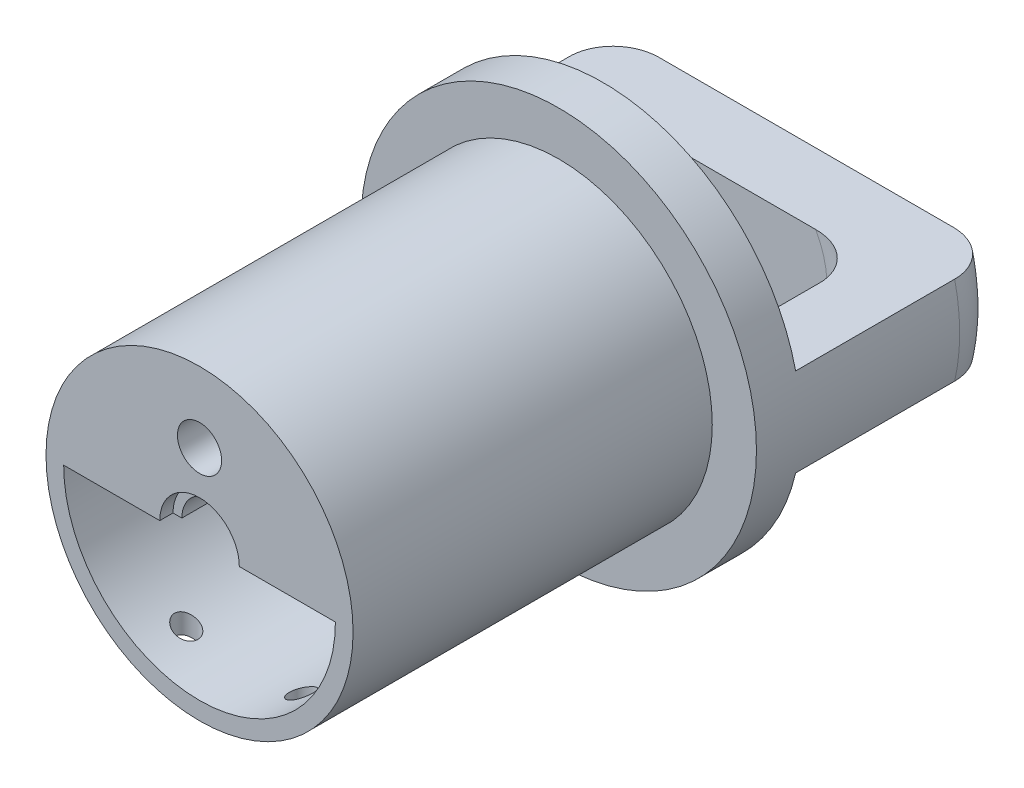
SolidWorks part; units mm, degrees
ref_plane "Plan de face" through (0, 0, 0) normal (0, 0, 1) x (1, 0, 0)
ref_plane "Plan de dessus" through (0, 0, 0) normal (0, 1, 0) x (1, 0, 0)
ref_plane "Plan de droite" through (0, 0, 0) normal (1, 0, 0) x (0, 0, -1)
sketch "Esquisse1" plane through (0, 0, 0) normal (0, 0, 1) x (1, 0, 0)
  circle A0 centre (0, 0) radius 34.75
  circle A1 centre (0, 0) radius 30.75
  dimension "D1" = 69.5
  dimension "D2" = 4
extrude "Boss.-Extru.1" add sketch "Esquisse1" along normal blind 91.3
sketch "Esquisse2" plane through (0, 0, 0) normal (0, 0, 1) x (1, 0, 0)
  circle A0 centre (0, 0) radius 34.75
  circle A2 centre (0, 0) radius 44.75
  circle A4 centre (0, 0) radius 34.75 construction
  dimension "D1" = 10
extrude "Boss.-Extru.2" add sketch "Esquisse2" along normal blind 10
sketch "Esquisse3" plane through (0, 0, 91.3) normal (0, 0, 1) x (1, 0, 0)
  circle A0 centre (0, 0) radius 45
extrude "Boss.-Extru.3" add sketch "Esquisse3" against normal blind 20
sketch "Esquisse4" plane through (0, 0, 0) normal (0, 1, 0) x (1, 0, 0)
  line L0 (0, -96.3) -> (0, -71.3) construction
  line L1 (-11.15, -96.3) -> (11.15, -96.3) construction
  line L2 (30.75, -71.3) -> (-30.75, -71.3) construction
  line L3 (0, -78.6) -> (-9, -78.6) construction
  line L5 (8, -78.6) -> (-8, -78.6) construction
  line L6 (-9, -78.6) -> (-9, -82.3)
  line L7 (-9, -82.3) -> (-7, -82.3)
  line L8 (-7, -82.3) -> (-7, -88.3)
  line L9 (-7, -88.3) -> (-9, -88.3)
  line L10 (-9, -88.3) -> (-9, -91.3)
  line L11 (-9, -91.3) -> (-7.25, -91.3)
  line L12 (-7.25, -91.3) -> (-7.25, -92.8)
  line L13 (-7.25, -92.8) -> (-9, -92.8)
  line L14 (-9, -92.8) -> (-9, -93.8)
  line L15 (-9, -93.8) -> (-7.25, -93.8)
  line L16 (-7.25, -93.8) -> (-7.25, -95.3)
  line L17 (-7.25, -95.3) -> (-12.15, -95.3)
  line L18 (-12.15, -95.3) -> (-12.15, -96.3)
  line L19 (-12.15, -96.3) -> (0, -96.3)
  line L20 (0, -96.3) -> (0, -71.3)
  line L21 (0, -71.3) -> (-10, -71.3)
  line L22 (-10, -71.3) -> (-9, -78.6)
  dimension "D1" = 10
  dimension "D2" = 9
  dimension "D3" = 7
  dimension "D4" = 9
  dimension "D5" = 7.25
  dimension "D6" = 9
  dimension "D7" = 7.25
  dimension "D8" = 12.15
  dimension "D9" = 3.7
  dimension "D10" = 6
  dimension "D11" = 1.5
  dimension "D12" = 1
  dimension "D13" = 3
  dimension "D14" = 1
revolve "Enlèvement de matière-Révolution1" cut sketch "Esquisse4" angle 360 about L20
sketch "Esquisse5" plane through (0, 0, 71.3) normal (0, 0, -1) x (-1, 0, 0)
  line L0 (-30.75, 0) -> (30.75, 0)
  circle A0 centre (0, 0) radius 30.75 construction
  arc A1 (-30.75, 0) -> (30.75, 0) centre (0, 0) ccw
  point P10 (0, 0)
extrude "Enlèv. mat.-Extru.1" cut sketch "Esquisse5" against normal blind 20
ref_plane "Plan1" through (0, -34.75, 0) normal (0, -1, 0) x (0, 0, -1)
sketch "Esquisse6" plane through (0, -34.75, 0) normal (0, -1, 0) x (0, 0, -1)
  circle A0 centre (-81.3, -13) radius 2.65 construction
  circle A1 centre (-81.3, 13) radius 2.65 construction
  circle A2 centre (-81.3, -13) radius 2.65
  circle A3 centre (-81.3, 13) radius 2.65
extrude "Enlèv. mat.-Extru.2" cut sketch "Esquisse6" against normal blind 10
sketch "Esquisse9" plane through (0, 0, 0) normal (0, 0, -1) x (-1, 0, 0)
  line L0 (0, 0) -> (-60, 0) construction
  line L1 (0, 0) -> (60, 0) construction
  line L2 (-43.6184, 10) -> (-29.0786, 10)
  line L3 (-43.6184, -10) -> (-29.0786, -10)
  line L4 (29.0786, -10) -> (43.6184, -10)
  line L5 (43.6184, 10) -> (29.0786, 10)
  circle A1 centre (0, 0) radius 30.75 construction
  arc A2 (-43.6184, 10) -> (-43.6184, -10) centre (0, 0) ccw
  arc A3 (-29.0786, 10) -> (-29.0786, -10) centre (0, 0) ccw
  arc A4 (43.6184, -10) -> (43.6184, 10) centre (0, 0) ccw
  arc A5 (29.0786, -10) -> (29.0786, 10) centre (0, 0) ccw
  circle A7 centre (0, 0) radius 44.75 construction
  dimension "D1" = 10
  dimension "D2" = 10
  dimension "D3" = 10
extrude "Boss.-Extru.4" add sketch "Esquisse9" along normal blind 30
sketch "Esquisse10" plane through (0, -10, 0) normal (0, -1, 0) x (1, 0, 0)
  line L0 (43.6184, -30) -> (43.6184, 0) construction
  line L1 (-43.6184, -30) -> (43.6184, -30)
  line L2 (-43.6184, -30) -> (-43.6184, -46)
  line L3 (-43.6184, -46) -> (43.6184, -46)
  line L4 (43.6184, -30) -> (43.6184, -46)
  line L5 (-43.6184, -30) -> (-43.6184, 0) construction
  dimension "D1" = 16
extrude "Boss.-Extru.5" add sketch "Esquisse10" against normal up to surface (20 mm away) up to face at (-36.3485, 10, -15)
sketch "Esquisse11" plane through (0, 0, -30) normal (0, 0, -1) x (-1, 0, 0)
  line L1 (43.6184, 10) -> (43.6184, -10)
  line L2 (43.6184, 10) -> (43.6184, -10)
  line L3 (-43.6184, -10) -> (-43.6184, 10)
  line L4 (-43.6184, -10) -> (-43.6184, 10)
  arc A1 (43.6184, -10) -> (43.6184, 10) centre (0, 0) ccw
  arc A3 (-43.6184, 10) -> (-43.6184, -10) centre (0, 0) ccw
  arc A4 (-43.6184, 10) -> (-43.6184, -10) centre (0, 0) ccw
  arc A6 (43.6184, -10) -> (43.6184, 10) centre (0, 0) ccw
  dimension "D1" = 0
  dimension "D2" = 0
extrude "Boss.-Extru.6" add sketch "Esquisse11" along normal up to surface (16 mm away) up to face at (0, 0, -46)
fillet "Congé1" radius 10 4 edges at (30.75, 0, -30) (-30.75, 0, -30) (-44.75, 0, -46) (44.75, 0, -46)
sketch "Esquisse12" plane through (0, 0, 71.3) normal (0, 0, -1) x (-1, 0, 0)
  circle A0 centre (0, 0) radius 34.75 construction
  circle A1 centre (0, 0) radius 45
  circle A2 centre (0, 0) radius 45
  circle A3 centre (0, 0) radius 34.75
  dimension "D1" = 0
extrude "Enlèv. mat.-Extru.4" cut sketch "Esquisse12" against normal blind 21
sketch "Esquisse13" plane through (0, 0, 91.3) normal (0, 0, 1) x (1, 0, 0)
  line L0 (0, 34.75) -> (0, -34.75) construction
  circle A0 centre (0, 0) radius 34.75 construction
  circle A1 centre (0, 18.75) radius 5
  dimension "D2" = 10
  dimension "D1" = 16
extrude "Enlèv. mat.-Extru.5" cut sketch "Esquisse13" against normal blind 30
sketch "Esquisse14" plane through (0, 0, 0) normal (0, -1, 0) x (1, 0, 0)
  circle A0 centre (13, 81.3) radius 2.65 construction
  circle A1 centre (13, 81.3) radius 2.65
  circle A2 centre (-13, 81.3) radius 2.65 construction
  circle A3 centre (-13, 81.3) radius 2.65
extrude "Enlèv. mat.-Extru.6" cut sketch "Esquisse14" against normal blind 12
sketch "Esquisse15" plane through (0, 0, 71.3) normal (0, 0, -1) x (-1, 0, 0)
  line L1 (-17, 6) -> (-9, 6)
  line L2 (-17, 6) -> (-17, 11)
  line L3 (-17, 11) -> (-9, 11)
  line L4 (-9, 6) -> (-9, 11)
  line L5 (-10, 0) -> (-30.75, 0) construction
  line L7 (-15.65, 12) -> (-10.35, 12) construction
  line L8 (-15.65, 12) -> (-10.35, 12) construction
  line L9 (0, 0) -> (0, 23.75) construction
  line L10 (17, 6) -> (17, 11)
  line L11 (17, 6) -> (9, 6)
  line L12 (9, 6) -> (9, 11)
  line L13 (17, 11) -> (9, 11)
  circle A0 centre (0, 18.75) radius 5 construction
  point P8 (-13, 12)
  point P9 (-13, 11)
  dimension "D1" = 11
  dimension "D2" = 5
  dimension "D3" = 8
extrude "Enlèv. mat.-Extru.7" cut sketch "Esquisse15" against normal blind 15
